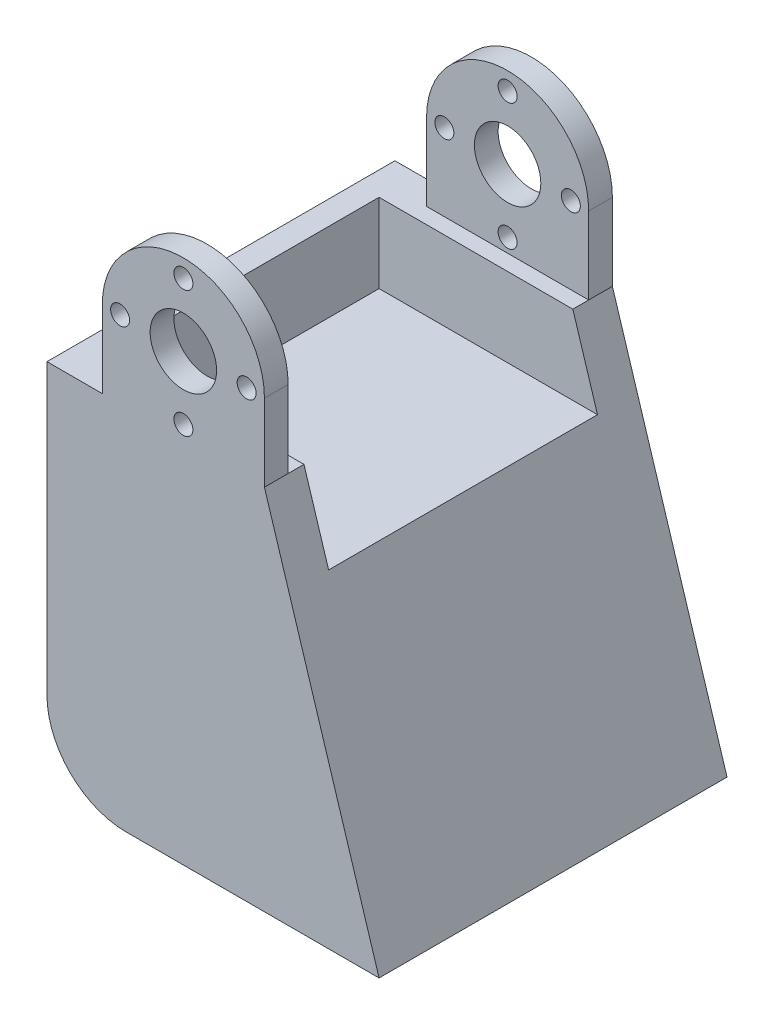
SolidWorks part; units mm, degrees
ref_plane "Front Plane" through (0, 0, 0) normal (0, 0, 1) x (1, 0, 0)
ref_plane "Top Plane" through (0, 0, 0) normal (0, 1, 0) x (1, 0, 0)
ref_plane "Right Plane" through (0, 0, 0) normal (1, 0, 0) x (0, 0, -1)
sketch "Sketch1" plane through (0, 0, 0) normal (0, 0, 1) x (1, 0, 0)
  line L0 (0, 0) -> (0, -100) construction
  line L1 (0, -100) -> (-70, -100) construction
  line L2 (-10.25, -60) -> (-70, -60) construction
  line L4 (-10.25, 0) -> (10.25, 0)
  line L5 (-10.25, 0) -> (-10.25, -60)
  line L7 (10.25, 0) -> (10.25, -60)
  line L8 (-10.25, 0) -> (10.25, 0)
  line L9 (-10.25, 0) -> (-10.25, -100)
  line L10 (-10.25, -100) -> (10.25, -100)
  line L11 (10.25, 0) -> (10.25, -100)
  circle A0 centre (0, 0) radius 10.25
  circle A1 centre (0, 0) radius 8
  circle A2 centre (0, 0) radius 4.2
  circle A3 centre (0, 8) radius 1.2
  circle A4 centre (8, 0) radius 1.2
  circle A5 centre (0, -8) radius 1.2
  circle A6 centre (-8, 0) radius 1.2
  point P16 (0, 0)
  dimension "D1" = 20.5
  dimension "D2" = 16
  dimension "D3" = 8.4
  dimension "D4" = 2.4
  dimension "D6" = 100
  dimension "D7" = 70
  dimension "D8" = 40
  dimension "D5" = 4
extrude "Boss-Extrude1" add sketch "Sketch1" along normal blind 22 and the other way blind 22 contours A0 L5 L7 | A6 L4 A0 A4 A1 A5 | A6 A1 A5 A4 L4 A2 | A6 L4 A2 A4 A1 A3 | A6 A1 A3 A4 L4 A0 region at (8.972, 1.0478, 0) region at (9.725, -0.2292, 0) region at (6.9906, -0.9364, 0) region at (5.5, 0.1769, 0) region at (0, -53.9967, 0)
sketch "Sketch2" plane through (-10.25, 0, 0) normal (-1, 0, 0) x (0, 0, 1)
  line L0 (22, 10.25) -> (-22, 10.25) construction
  line L1 (-19, 10.25) -> (19, 10.25)
  line L2 (-19, 10.25) -> (-19, -9.75)
  line L3 (-19, -9.75) -> (19, -9.75)
  line L4 (19, 10.25) -> (19, -9.75)
  line L5 (22, 0) -> (22, 10.25) construction
  line L6 (-22, 10.25) -> (-22, 0) construction
  dimension "D1" = 3
  dimension "D2" = 3
  dimension "D3" = 20
extrude "Cut-Extrude1" cut sketch "Sketch2" against normal through all
sketch "Sketch3" plane through (0, -9.75, 0) normal (0, 1, 0) x (1, 0, 0)
  line L1 (-10.25, 22) -> (-17.25, 22)
  line L2 (-10.25, 22) -> (-10.25, -22)
  line L3 (-10.25, -22) -> (-17.25, -22)
  line L4 (-17.25, 22) -> (-17.25, -22)
  line L5 (10.25, 22) -> (17.25, 22)
  line L6 (10.25, 22) -> (10.25, -22)
  line L7 (10.25, -22) -> (17.25, -22)
  line L8 (17.25, 22) -> (17.25, -22)
  dimension "D1" = 7
  dimension "D2" = 7
extrude "Boss-Extrude2" add sketch "Sketch3" against normal blind 65.5
sketch "Sketch23" plane through (0, 0, 22) normal (0, 0, 1) x (1, 0, 0)
  line L0 (10.25, -75.25) -> (17.25, -75.25) construction
  line L4 (10.25, -100) -> (-10.25, -100)
  line L5 (10.25, -100) -> (10.25, -75.25)
  line L6 (10.25, -75.25) -> (-10.25, -75.25)
  line L7 (-10.25, -100) -> (-10.25, -75.25)
  circle A0 centre (0, -85) radius 5
  circle A1 centre (0, 0) radius 4.2 construction
  circle A2 centre (0, -85) radius 8
  circle A3 centre (0, -77) radius 1.2
  circle A5 centre (8, -85) radius 1.2
  circle A6 centre (0, -93) radius 1.2
  circle A7 centre (-8, -85) radius 1.2
  circle A8 centre (0, -85) radius 10.25
  point P20 (0, -85)
  line M11 (-10.25, -100) -> (10.25, -100)
  line M12 (10.25, -100) -> (10.25, -75.25)
  dimension "D1" = 85
  dimension "D2" = 9.75
  dimension "D3" = 2.4
  dimension "D4" = 4
extrude "Cut-Extrude2" cut sketch "Sketch23" against normal through all contours A8 L7 M11 M12 | A2 A7 | A2 A7 | A2 A3 | A2 A3 | A2 A5 | A2 A5 | A2 A6 | A2 A6 | A0 region at (0, -96.1486, 22) region at (0, -85, 22) region at (7.4748, -85, 22) region at (8.4927, -85, 22) region at (0, -77.5252, 22) region at (0, -76.5073, 22) region at (0, -93.4927, 22) region at (0, -92.4748, 22) region at (-7.4748, -85, 22) region at (-8.4927, -85, 22)
sketch "Sketch24" plane through (0, -9.75, 0) normal (0, 1, 0) x (1, 0, 0)
  line L0 (17.25, -22) -> (17.25, 22) construction
  line L1 (-14.25, 17) -> (14.25, 17)
  line L2 (-14.25, 17) -> (-14.25, -17)
  line L3 (-14.25, -17) -> (14.25, -17)
  line L4 (14.25, 17) -> (14.25, -17)
  line L5 (-17.25, 22) -> (-17.25, -22) construction
  line L6 (10.25, 19) -> (-10.25, 19) construction
  line L7 (10.25, -19) -> (-10.25, -19) construction
  dimension "D1" = 3
  dimension "D2" = 3
  dimension "D3" = 2
  dimension "D4" = 2
extrude "Cut-Extrude3" cut sketch "Sketch24" against normal through all
sketch "Sketch26" plane through (0, 0, 22) normal (0, 0, 1) x (1, 0, 0)
  line L0 (-17.25, -75.25) -> (-17.25, -9.75) construction
  line L1 (14.25, -96.25) -> (-14.25, -96.25)
  line L2 (14.25, -96.25) -> (14.25, -49.75)
  line L3 (14.25, -49.75) -> (-14.25, -49.75)
  line L4 (-14.25, -96.25) -> (-14.25, -49.75)
  line L5 (17.25, -75.25) -> (17.25, -9.75) construction
  line L7 (-14.25, -49.75) -> (14.25, -49.75)
  line L8 (-14.25, -49.75) -> (-14.25, -56.5328)
  line L10 (14.25, -49.75) -> (14.25, -56.5328)
  line L11 (-14.25, -49.75) -> (14.25, -49.75)
  line L12 (-14.25, -49.75) -> (-14.25, -56.25)
  line L13 (-14.25, -56.25) -> (14.25, -56.25)
  line L14 (14.25, -49.75) -> (14.25, -56.25)
  line L15 (14.25, -56.25) -> (17.25, -56.25)
  line L16 (14.25, -56.25) -> (14.25, -75.25)
  line L17 (14.25, -75.25) -> (17.25, -75.25)
  line L18 (17.25, -56.25) -> (17.25, -75.25)
  line L19 (-17.25, -75.25) -> (-14.25, -75.25)
  line L20 (-17.25, -75.25) -> (-17.25, -56.25)
  line L21 (-17.25, -56.25) -> (-14.25, -56.25)
  line L22 (-14.25, -75.25) -> (-14.25, -56.25)
  arc A0 (-10.25, -85) -> (10.25, -85) centre (0, -85) ccw construction
  circle A1 centre (-11, -53) radius 1.45
  circle A2 centre (11, -53) radius 1.45
  circle M4 centre (0, -93) radius 1.2
  circle M5 centre (8, -85) radius 1.2
  circle M6 centre (0, -77) radius 1.2
  circle M7 centre (-8, -85) radius 1.2
  circle M8 centre (0, -85) radius 5
  line M14 (-10.25, -75.25) -> (-10.25, -85)
  arc M15 (-10.25, -85) -> (10.25, -85) centre (0, -85) ccw
  line M16 (10.25, -85) -> (10.25, -75.25)
  line M17 (10.25, -75.25) -> (17.25, -75.25)
  line M18 (17.25, -75.25) -> (17.25, -9.75)
  line M24 (-17.25, -9.75) -> (-17.25, -75.25)
  line M25 (-17.25, -75.25) -> (-10.25, -75.25)
  dimension "D4" = 2.9
  dimension "D5" = 3.25
  dimension "D6" = 3.25
  dimension "D1" = 3
  dimension "D2" = 3
  dimension "D3" = 11.25
  dimension "D8" = 3.25
  dimension "D9" = 46.5
  dimension "D7" = 2
extrude "Cut-Extrude6" cut sketch "Sketch26" against normal through all contours L13 L4 L2 M25 M14 M15 M16 M17 M5 M7 M8 M6 M4 | L21 L4 M24 M25 | L15 L2 M17 M18 | A1 | A2 region at (0, -71.8107, 22) region at (15.75, -65.75, 22) region at (-15.75, -65.75, 22) region at (-11, -53, 22) region at (11, -53, 22)
sketch "Sketch27" plane through (0, -56.25, 0) normal (0, -1, 0) x (1, 0, 0)
  line L0 (-14.25, 17) -> (14.25, 17) construction
  line L1 (-14.85, -17.6) -> (14.85, -17.6)
  line L2 (-14.85, -17.6) -> (-14.85, 17.6)
  line L3 (-14.85, 17.6) -> (14.85, 17.6)
  line L4 (14.85, -17.6) -> (14.85, 17.6)
  line L5 (-14.85, -17.6) -> (14.85, 17.6) construction
  line L6 (-14.85, 17.6) -> (14.85, -17.6) construction
  line L7 (14.25, 17) -> (14.25, -17) construction
  point P0 (0, 0)
  dimension "D1" = 0.6
  dimension "D2" = 0.6
extrude "Cut-Extrude8" cut sketch "Sketch27" against normal through all
sketch "Sketch29" plane through (0, 0, -22) normal (0, 0, -1) x (-1, 0, 0)
  line L1 (-17.25, -9.75) -> (-10.25, -9.75)
  line L2 (-17.25, -9.75) -> (-17.25, -39.75)
  line L3 (-17.25, -39.75) -> (-10.25, -39.75)
  line L4 (-10.25, -9.75) -> (-10.25, -39.75)
  dimension "D1" = 30
extrude "Cut-Extrude10" cut sketch "Sketch29" against normal through all
chamfer "Chamfer2" distance 5 angle 45 1 edges at (-17.25, -56.25, 0)
sketch "Sketch30" plane through (0, 0, 0) normal (0, 0, 1) x (1, 0, 0)
  line L0 (10.25, -9.75) -> (32.75, -56.25)
  line L1 (-17.25, -9.75) -> (17.25, -9.75)
  line L2 (-17.25, -9.75) -> (-17.25, -56.25)
  line L3 (-17.25, -56.25) -> (17.25, -56.25)
  line L4 (17.25, -9.75) -> (17.25, -56.25)
  line L5 (32.75, -56.25) -> (17.25, -56.25)
  line L6 (10.25, -9.75) -> (24.75, -56.25)
  dimension "D1" = 50
  dimension "D2" = 42
extrude "Boss-Extrude4" add sketch "Sketch30" along normal blind 22 and the other way blind 22 contours L6 L4 L5 | L6 L1 L2 L3 L4 region at (-0.7682, -33.812, 0) region at (19.75, -48.2328, 0)
sketch "Sketch31" plane through (0, -9.75, 0) normal (0, 1, 0) x (1, 0, 0)
  line L0 (-17.25, 22) -> (-17.25, -22) construction
  line L1 (-14.25, 17) -> (14.25, 17)
  line L2 (-14.25, 17) -> (-14.25, -17)
  line L3 (-14.25, -17) -> (14.25, -17)
  line L4 (14.25, 17) -> (14.25, -17)
  line L7 (10.25, -19) -> (-10.25, -19) construction
  line L8 (-10.25, 19) -> (10.25, 19) construction
  dimension "D1" = 3
  dimension "D2" = 28.5
  dimension "D3" = 2
  dimension "D4" = 2
extrude "Cut-Extrude11" cut sketch "Sketch31" against normal blind 10
fillet "Fillet1" radius 10 1 edges at (-17.25, -56.25, 0)
